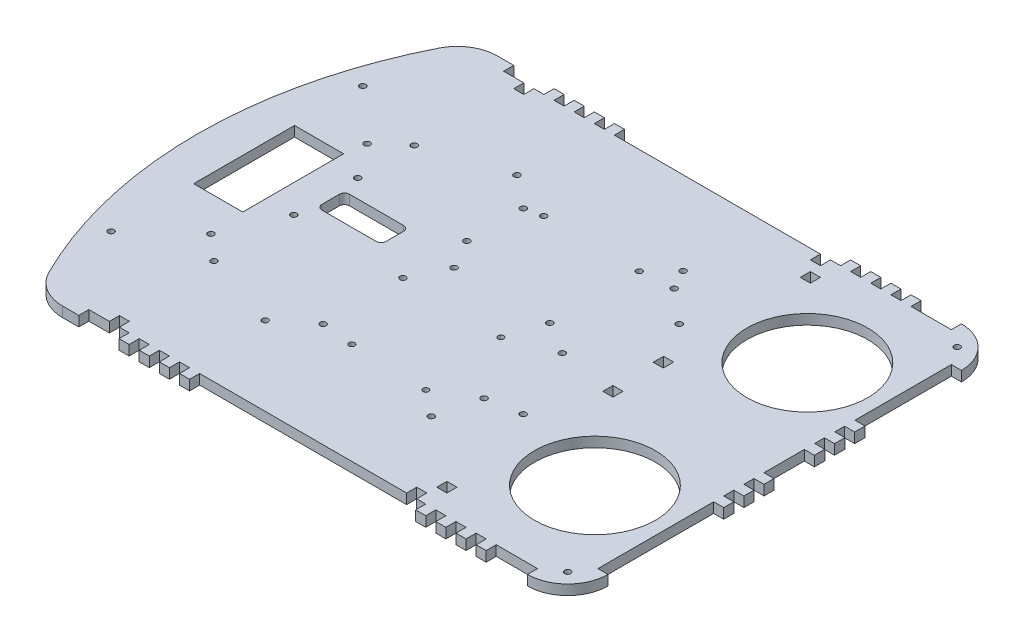
SolidWorks part; units mm, degrees
ref_plane "Front Plane" through (0, 0, 0) normal (0, 0, 1) x (1, 0, 0)
ref_plane "Top Plane" through (0, 0, 0) normal (0, 1, 0) x (1, 0, 0)
ref_plane "Right Plane" through (0, 0, 0) normal (1, 0, 0) x (0, 0, -1)
sketch "main_base_sketch" plane through (0, 0, 0) normal (0, 1, 0) x (1, 0, 0)
  line L1 (111.125, 92.7285) -> (111.125, 23.3533) construction
  line L2 (111.125, -38.1761) -> (111.125, 0) construction
  line L3 (111.125, -99.4864) -> (111.125, -136.4602) construction
  line L4 (111.125, -38.1761) -> (111.125, -99.4864) construction
  line L5 (111.125, 23.3533) -> (111.125, 0) construction
  line L7 (111.125, 92.7285) -> (111.125, 23.3533) construction
  line L9 (111.125, 0) -> (111.125, 23.3533) construction
  line L10 (111.125, 0) -> (111.125, -38.1761) construction
  line L11 (111.125, 0) -> (111.125, -38.1761) construction
  line L20 (-111.125, 0) -> (111.125, 0) construction
  line L22 (111.125, 130.8285) -> (117.475, 130.8285) construction
  line L24 (-94.9614, 130.8285) -> (-94.9614, 124.4785) construction
  line L25 (-94.9614, 124.4785) -> (-82.2614, 124.4785)
  line L26 (187.325, 130.8285) -> (187.325, 124.4785)
  line L27 (-95.6016, -142.8102) -> (111.125, -142.8102) construction
  line L28 (-95.6016, -142.8102) -> (-95.6016, -136.4602)
  line L29 (-95.6016, -136.4602) -> (-82.6643, -136.4602)
  line L30 (187.325, -142.8102) -> (187.325, -136.4602)
  line L32 (-94.9614, 130.8285) -> (-25.1114, 130.8285) construction
  line L33 (111.125, -142.8102) -> (187.325, -142.8102) construction
  line L34 (111.125, -136.4602) -> (111.125, -142.8102) construction
  line L36 (111.125, -136.4602) -> (111.125, -142.8102) construction
  line L37 (-56.8614, 130.8285) -> (-50.5114, 130.8285)
  line L38 (111.125, 12.7) -> (117.4276, 12.7)
  line L39 (-42.259, -8.6817) -> (-76.4089, -8.6817)
  line L40 (-39.084, -5.5067) -> (-39.084, 5.5067)
  line L41 (-42.259, 8.6817) -> (-76.4089, 8.6817)
  line L42 (-79.5839, -5.5067) -> (-79.5839, 5.5067)
  line L43 (-39.084, -8.6817) -> (-79.5839, 8.6817) construction
  line L44 (-39.084, 8.6817) -> (-79.5839, -8.6817) construction
  line L46 (61.595, 63.5) -> (93.345, 63.5) construction
  line L47 (61.595, 63.5) -> (61.595, -63.5) construction
  line L48 (61.595, -63.5) -> (93.345, -63.5) construction
  line L49 (93.345, 63.5) -> (93.345, -63.5) construction
  line L50 (61.595, 63.5) -> (93.345, -63.5) construction
  line L51 (61.595, -63.5) -> (93.345, 63.5) construction
  line L52 (111.125, 12.7) -> (111.125, 19.2555)
  line L53 (111.125, 23.3533) -> (111.125, 0) construction
  line L54 (111.125, 19.2555) -> (117.4276, 19.2555)
  line L55 (-94.9614, 130.8285) -> (-25.1114, 130.8285) construction
  line L58 (111.125, 124.4785) -> (111.125, 92.7285) construction
  line L61 (-95.6016, -142.8102) -> (111.125, -142.8102) construction
  line L62 (111.125, -99.4864) -> (111.125, -136.4602) construction
  line L63 (111.125, 130.8285) -> (117.475, 130.8285) construction
  line L64 (111.125, 124.4785) -> (111.125, 92.7285) construction
  line L65 (111.125, -142.8102) -> (187.325, -142.8102) construction
  line L66 (212.725, 105.4285) -> (212.725, -117.4102) construction
  line L67 (117.4276, 12.7) -> (117.4276, 19.2555)
  line L68 (111.125, -12.7) -> (117.475, -12.7)
  line L69 (111.125, -12.7) -> (111.125, -19.05)
  line L70 (111.125, -19.05) -> (117.475, -19.05)
  line L71 (117.475, -12.7) -> (117.475, -19.05)
  line L72 (111.125, 105.4285) -> (117.475, 105.4285)
  line L73 (111.125, 105.4285) -> (111.125, 111.7785)
  line L74 (111.125, 111.7785) -> (117.475, 111.7785)
  line L75 (117.475, 105.4285) -> (117.475, 111.7785)
  line L76 (111.125, -117.4102) -> (117.475, -117.4102)
  line L77 (111.125, -117.4102) -> (111.125, -123.7602)
  line L78 (111.125, -123.7602) -> (117.475, -123.7602)
  line L79 (117.475, -117.4102) -> (117.475, -123.7602)
  line L80 (212.725, 105.4285) -> (206.375, 105.4285)
  line L81 (212.725, 105.4285) -> (212.725, -117.4102) construction
  line L82 (212.725, -117.4102) -> (206.375, -117.4102)
  line L84 (-69.5614, 130.8285) -> (-63.2114, 130.8285)
  line L85 (-69.5614, 130.8285) -> (-69.5614, 124.4785)
  line L86 (-69.5614, 124.4785) -> (-63.2114, 124.4785) construction
  line L87 (-63.2114, 130.8285) -> (-63.2114, 124.4785)
  line L88 (-56.8614, 130.8285) -> (-56.8614, 124.4785)
  line L89 (-56.8614, 124.4785) -> (-50.5114, 124.4785) construction
  line L90 (-50.5114, 130.8285) -> (-50.5114, 124.4785)
  line L91 (-44.1614, 130.8285) -> (-37.8114, 130.8285)
  line L92 (-44.1614, 130.8285) -> (-44.1614, 124.4785)
  line L93 (-44.1614, 124.4785) -> (-37.8114, 124.4785) construction
  line L94 (-37.8114, 130.8285) -> (-37.8114, 124.4785)
  line L95 (-31.4614, 130.8285) -> (-25.1114, 130.8285)
  line L96 (-31.4614, 130.8285) -> (-31.4614, 124.4785)
  line L97 (-31.4614, 124.4785) -> (-25.1114, 124.4785) construction
  line L98 (-25.1114, 130.8285) -> (-25.1114, 124.4785)
  line L99 (-69.5614, 124.4785) -> (-63.2114, 124.4785) construction
  line L100 (-63.2114, 124.4785) -> (-56.8614, 124.4785)
  line L101 (-56.8614, 124.4785) -> (-50.5114, 124.4785) construction
  line L102 (-50.5114, 124.4785) -> (-44.1614, 124.4785)
  line L103 (-44.1614, 124.4785) -> (-37.8114, 124.4785) construction
  line L104 (-37.8114, 124.4785) -> (-31.4614, 124.4785)
  line L105 (-31.4614, 124.4785) -> (-25.1114, 124.4785) construction
  line L106 (-25.1114, 124.4785) -> (104.775, 124.4785)
  line L107 (149.225, 130.8285) -> (142.875, 130.8285)
  line L108 (161.925, 130.8285) -> (155.575, 130.8285)
  line L109 (161.925, 130.8285) -> (161.925, 124.4785)
  line L110 (161.925, 124.4785) -> (155.575, 124.4785) construction
  line L111 (155.575, 130.8285) -> (155.575, 124.4785)
  line L112 (149.225, 130.8285) -> (149.225, 124.4785)
  line L114 (142.875, 130.8285) -> (142.875, 124.4785)
  line L115 (136.525, 130.8285) -> (130.175, 130.8285)
  line L116 (136.525, 130.8285) -> (136.525, 124.4785)
  line L118 (130.175, 130.8285) -> (130.175, 124.4785)
  line L119 (123.825, 130.8285) -> (117.475, 130.8285) construction
  line L120 (123.825, 130.8285) -> (123.825, 124.4785)
  line L122 (117.475, 130.8285) -> (117.475, 124.4785) construction
  line L123 (117.475, 130.8285) -> (123.825, 130.8285) construction
  line L124 (206.375, 105.4285) -> (206.375, 44.6555)
  line L127 (117.475, 130.8285) -> (117.475, 124.4785) construction
  line L128 (117.475, 130.8285) -> (117.475, 124.4785) construction
  line L129 (145.8534, 124.4785) -> (130.175, 124.4785) [skipped]
  line L130 (149.225, 124.4785) -> (146.7264, 124.4785) [skipped]
  line L131 (123.825, 124.4785) -> (130.175, 124.4785)
  line L132 (136.525, 124.4785) -> (142.875, 124.4785)
  line L133 (149.225, 124.4785) -> (155.575, 124.4785)
  line L134 (161.925, 124.4785) -> (187.325, 124.4785)
  line L135 (133.0367, 124.4785) -> (117.475, 124.4785) [skipped]
  line L136 (123.825, 130.8285) -> (187.325, 130.8285) construction
  line L137 (117.475, 130.8285) -> (123.825, 130.8285) construction
  line L138 (123.825, 130.8285) -> (187.325, 130.8285) construction
  line L139 (-25.1114, 130.8285) -> (111.125, 130.8285) construction
  line L140 (-25.1114, 130.8285) -> (111.125, 130.8285) construction
  line L141 (111.125, 130.8285) -> (111.125, 124.4785) construction
  line L142 (111.125, 130.8285) -> (111.125, 124.4785) construction
  line L143 (123.825, 130.8285) -> (117.475, 130.8285)
  line L144 (117.475, 130.8285) -> (117.475, 124.4785)
  line L151 (206.375, -12.7) -> (212.725, -12.7)
  line L152 (206.375, -12.7) -> (206.375, -19.05) construction
  line L153 (206.375, -19.05) -> (212.725, -19.05)
  line L154 (212.725, -12.7) -> (212.725, -19.05)
  line L155 (206.375, -12.7) -> (206.375, -19.05) construction
  line L156 (206.375, -19.05) -> (206.375, -25.4)
  line L157 (206.375, 19.2555) -> (212.725, 19.2555)
  line L158 (212.725, 19.2555) -> (212.725, 12.7)
  line L159 (212.725, 12.7) -> (206.375, 12.7)
  line L160 (206.375, 24.1792) -> (206.375, 19.2555)
  line L161 (206.375, 12.7) -> (206.375, -12.7)
  line L162 (-70.2016, -136.4602) -> (-70.2016, -142.8102)
  line L163 (-70.2016, -142.8102) -> (-63.8516, -142.8102)
  line L164 (-63.8516, -142.8102) -> (-63.8516, -136.4602)
  line L165 (-70.2016, -136.4602) -> (-63.8516, -136.4602) construction
  line L166 (-63.8516, -136.4602) -> (-57.5016, -136.4602)
  line L167 (-57.5016, -142.8102) -> (-51.1516, -142.8102)
  line L168 (-57.5016, -136.4602) -> (-57.5016, -142.8102)
  line L169 (-51.1516, -142.8102) -> (-51.1516, -136.4602)
  line L170 (-44.8016, -142.8102) -> (-38.4516, -142.8102)
  line L171 (-44.8016, -136.4602) -> (-44.8016, -142.8102)
  line L172 (-38.4516, -142.8102) -> (-38.4516, -136.4602)
  line L173 (-32.1016, -142.8102) -> (-25.7516, -142.8102)
  line L174 (-32.1016, -136.4602) -> (-32.1016, -142.8102)
  line L175 (-25.7516, -142.8102) -> (-25.7516, -136.4602)
  line L176 (-57.5016, -136.4602) -> (-51.1516, -136.4602) construction
  line L177 (-51.1516, -136.4602) -> (-44.8016, -136.4602)
  line L178 (-44.8016, -136.4602) -> (-38.4516, -136.4602) construction
  line L179 (-38.4516, -136.4602) -> (-32.1016, -136.4602)
  line L180 (-32.1016, -136.4602) -> (-25.7516, -136.4602) construction
  line L181 (-25.7516, -136.4602) -> (104.775, -136.4602)
  line L182 (161.2847, -136.4602) -> (161.2847, -142.8102)
  line L183 (161.2847, -142.8102) -> (154.9347, -142.8102)
  line L184 (154.9347, -142.8102) -> (154.9347, -136.4602)
  line L185 (148.5847, -136.4602) -> (148.5847, -142.8102)
  line L186 (148.5847, -142.8102) -> (142.2347, -142.8102)
  line L187 (142.2347, -142.8102) -> (142.2347, -136.4602)
  line L188 (135.8847, -136.4602) -> (135.8847, -142.8102)
  line L189 (135.8847, -142.8102) -> (129.5347, -142.8102)
  line L190 (129.5347, -142.8102) -> (129.5347, -136.4602)
  line L191 (123.1847, -136.4602) -> (123.1847, -142.8102)
  line L192 (123.1847, -142.8102) -> (116.8347, -142.8102)
  line L193 (116.8347, -142.8102) -> (116.8347, -136.4602)
  line L194 (154.9347, -136.4602) -> (161.2847, -136.4602) construction
  line L195 (161.2847, -136.4602) -> (187.325, -136.4602)
  line L196 (142.2347, -136.4602) -> (148.5847, -136.4602) construction
  line L197 (148.5847, -136.4602) -> (154.9347, -136.4602)
  line L198 (129.5347, -136.4602) -> (135.8847, -136.4602) construction
  line L199 (135.8847, -136.4602) -> (142.2347, -136.4602)
  line L200 (116.8347, -136.4602) -> (123.1847, -136.4602) construction
  line L201 (123.1847, -136.4602) -> (129.5347, -136.4602)
  line L202 (212.725, 25.4) -> (206.375, 25.4)
  line L203 (212.725, 31.9555) -> (212.725, 25.4)
  line L204 (206.375, 31.9555) -> (212.725, 31.9555)
  line L205 (212.725, 38.1) -> (206.375, 38.1)
  line L206 (212.725, 44.6555) -> (212.725, 38.1)
  line L207 (206.375, 44.6555) -> (212.725, 44.6555)
  line L208 (206.375, 31.9555) -> (206.375, 25.4) construction
  line L209 (206.375, 25.4) -> (206.375, 24.1792)
  line L210 (206.375, 44.6555) -> (206.375, 38.1) construction
  line L211 (206.375, 38.1) -> (206.375, 31.9555)
  line L212 (206.375, -31.75) -> (212.725, -31.75)
  line L213 (212.725, -25.4) -> (212.725, -31.75)
  line L214 (206.375, -25.4) -> (212.725, -25.4)
  line L215 (206.375, -44.45) -> (212.725, -44.45)
  line L216 (212.725, -38.1) -> (212.725, -44.45)
  line L217 (206.375, -38.1) -> (212.725, -38.1)
  line L218 (206.375, -25.4) -> (206.375, -31.75) construction
  line L219 (206.375, -31.75) -> (206.375, -38.1)
  line L220 (206.375, -38.1) -> (206.375, -44.45) construction
  line L221 (206.375, -44.45) -> (206.375, -117.4102)
  line L225 (-95.5505, 130.8285) -> (-157.7358, 130.8285) construction
  line L229 (-131.2964, 28.9076) -> (-100.3373, 28.9076)
  line L230 (-131.2964, 28.9076) -> (-131.2964, -34.6891)
  line L231 (-131.2964, -34.6891) -> (-100.3373, -34.6891)
  line L238 (-100.3373, 28.9076) -> (-100.3373, -34.6891)
  line L248 (-94.9614, 130.8285) -> (-95.5505, 130.8285) construction
  line L254 (-94.9614, 130.8285) -> (-95.5505, 130.8285) construction
  line L257 (-94.9614, 130.8285) -> (-105.2412, 130.8285)
  line L258 (-95.5505, 130.8285) -> (-94.9614, 130.8285) construction
  line L259 (-95.6016, -142.8102) -> (-105.7982, -142.8102)
  line L260 (-94.9614, 124.4785) -> (-94.9614, 130.8285)
  line L261 (-94.9614, 130.8285) -> (-95.5505, 130.8285) construction
  line L262 (-82.2614, 124.4785) -> (-75.9114, 124.4785) construction
  line L263 (-82.2614, 124.4785) -> (-75.9114, 124.4785) construction
  line L264 (-82.2614, 124.4785) -> (-82.2614, 118.1285)
  line L265 (-82.2614, 118.1285) -> (-75.9114, 118.1285)
  line L266 (-75.9114, 124.4785) -> (-75.9114, 118.1285)
  line L267 (-97.1554, -142.8102) -> (-95.6016, -142.8102) construction
  line L269 (-75.9114, 124.4785) -> (-69.5614, 124.4785)
  line L270 (104.775, 124.4785) -> (111.125, 124.4785) construction
  line L271 (111.125, 124.4785) -> (104.775, 124.4785) construction
  line L272 (111.125, 124.4785) -> (111.125, 118.1285)
  line L274 (111.125, 118.1285) -> (104.775, 118.1285)
  line L280 (104.775, 124.4785) -> (104.775, 118.1285)
  line L281 (111.125, 124.4785) -> (117.475, 124.4785)
  line L282 (104.775, -136.4602) -> (111.125, -136.4602) construction
  line L285 (111.125, -136.4602) -> (104.775, -136.4602) construction
  line L286 (111.125, -136.4602) -> (111.125, -130.1018)
  line L289 (111.125, -130.1018) -> (104.775, -130.1018)
  line L291 (104.775, -136.4602) -> (104.775, -130.1018)
  line L292 (111.125, -136.4602) -> (116.8347, -136.4602)
  line L293 (-82.6643, -136.4602) -> (-76.4089, -136.4602) construction
  line L294 (-94.9614, 130.8285) -> (-95.5505, 130.8285) construction
  line L295 (-157.7358, 130.8285) -> (-157.7358, -142.8102) construction
  line L296 (-157.7358, -142.8102) -> (-97.1554, -142.8102) construction
  line L297 (-95.5505, 130.8285) -> (-157.7358, 130.8285) construction
  line L298 (-82.6643, -136.4602) -> (-76.4089, -136.4602) construction
  line L299 (-82.6643, -136.4602) -> (-82.6643, -130.1018)
  line L300 (-82.6643, -130.1018) -> (-76.4089, -130.1018)
  line L301 (-76.4089, -136.4602) -> (-76.4089, -130.1018)
  line L302 (-76.4089, -136.4602) -> (-70.2016, -136.4602)
  circle A0 centre (-82.6643, 55.7457) radius 1.905
  circle A1 centre (-13.8303, 55.7457) radius 1.905
  arc A2 (-76.4089, -8.6817) -> (-79.5839, -5.5067) centre (-76.4089, -5.5067) cw
  arc A3 (-42.259, -8.6817) -> (-39.084, -5.5067) centre (-42.259, -5.5067) ccw
  arc A4 (-39.084, 5.5067) -> (-42.259, 8.6817) centre (-42.259, 5.5067) ccw
  arc A5 (-76.4089, 8.6817) -> (-79.5839, 5.5067) centre (-76.4089, 5.5067) ccw
  circle A10 centre (-3.2843, 57.9936) radius 1.905
  circle A11 centre (-13.8303, 20.1549) radius 1.905
  circle A12 centre (-3.2843, 1.5294) radius 1.905
  circle A13 centre (-82.6643, 20.1549) radius 1.905
  circle A14 centre (-82.6643, -20.1549) radius 1.905
  circle A15 centre (-13.8303, -20.1549) radius 1.905
  circle A16 centre (-82.6643, -70.5685) radius 1.905
  circle A17 centre (-13.8303, -70.5685) radius 1.905
  circle A18 centre (6.29, -72.5476) radius 1.796
  circle A19 centre (54.55, -74.1351) radius 1.796
  circle A20 centre (49.47, -21.7476) radius 1.796
  circle A21 centre (57.0407, 1.5294) radius 1.905
  circle A22 centre (57.0407, 57.9936) radius 1.905
  circle A23 centre (-98.425, 41.8224) radius 1.905
  circle A24 centre (-34.0871, 71.9636) radius 1.905
  circle A25 centre (70.6863, 71.9636) radius 1.905
  circle A26 centre (98.425, 41.8224) radius 1.905
  circle A27 centre (98.425, -56.6452) radius 1.905
  circle A28 centre (70.6863, -86.7864) radius 1.905
  circle A29 centre (-34.0871, -86.7864) radius 1.905
  circle A30 centre (-98.425, -56.6452) radius 1.905
  circle A31 centre (77.47, -60.325) radius 1.905
  circle A32 centre (77.47, 59.5313) radius 1.905
  circle A33 centre (77.47, -10.9537) radius 1.905
  arc A34 (212.725, -117.4102) -> (187.325, -142.8102) centre (187.325, -117.4102) cw
  arc A35 (212.725, 105.4285) -> (187.325, 130.8285) centre (187.325, 105.4285) ccw
  circle A37 centre (160.02, 60.9785) radius 38.1
  circle A38 centre (160.02, -72.9602) radius 38.1
  arc A41 (-127.9188, 116.8691) -> (-128.5327, -128.7374) centre (116.7138, -6.5464) ccw
  arc A42 (-127.9188, 116.8691) -> (-105.2412, 130.8285) centre (-105.2412, 105.4285) cw
  arc A43 (-128.5327, -128.7374) -> (-105.7982, -142.8102) centre (-105.7982, -117.4102) ccw
  circle A44 centre (-131.2964, 71.9636) radius 1.905
  circle A45 centre (-131.2964, -86.7864) radius 1.905
  circle A46 centre (198.6177, 116.8691) radius 1.905
  circle A47 centre (198.6177, -128.7374) radius 1.905
  point P16 (-120.3614, 130.8285)
  point P19 (212.725, -142.8102)
  point P40 (-59.334, 0)
  point P46 (-121.0016, -142.8102)
  point P111 (77.47, -63.5)
  point P113 (77.47, 0)
  point P123 (0, 0)
  dimension "D1" = 3.175
  dimension "D44" = 3.81
  dimension "D45" = 3.81
  dimension "D46" = 3.81
  dimension "D47" = 3.592
  dimension "D48" = 3.592
  dimension "D49" = 3.592
  dimension "D7" = 63.5
  dimension "D12" = 25.4
  dimension "D13" = 25.4
  dimension "D21" = 63.5
  dimension "D24" = 76.2
  dimension "D26" = 76.2
  dimension "D14" = 25.4
  dimension "D30" = 3.81
  dimension "D31" = 6.35
  dimension "D8" = 4
  dimension "D9" = 40.4999
  dimension "D10" = 17.3633
  dimension "D11" = 4
  dimension "D15" = 104.7734
  dimension "D16" = 74.077
  dimension "D17" = 104.835
  dimension "D18" = 12.7
  dimension "D19" = 6.35
  dimension "D20" = 6.35
  dimension "D22" = 40.4387
  dimension "D23" = 54.0843
  dimension "D25" = 60.325
  dimension "D27" = 10.2799
  dimension "D28" = 10.1966
  dimension "D29" = 6.5555
  dimension "D32" = 6.35
  dimension "D33" = 6.35
  dimension "D34" = 68.834
  dimension "D35" = 48.26
  dimension "D36" = 6.35
  dimension "D37" = 20.1549
  dimension "D38" = 20.1549
  dimension "D39" = 56.4642
  dimension "D40" = 35.7997
  dimension "D41" = 54.0843
  dimension "D42" = 61.655
  dimension "D43" = 23.277
  dimension "D50" = 1.5875
  dimension "D51" = 127
  dimension "D52" = 31.75
  dimension "D53" = 17.78
  dimension "D54" = 3.175
  dimension "D55" = 3.9688
  dimension "D56" = 70.485
  dimension "D57" = 38.1
  dimension "D58" = 6.35
  dimension "D59" = 101.6
  dimension "D60" = 6.3026
  dimension "D61" = 12.7
  dimension "D62" = 12.7
  dimension "D63" = 6.35
  dimension "D64" = 6.35
  dimension "D65" = 6.35
  dimension "D66" = 6.35
  dimension "D67" = 12.7
  dimension "D68" = 12.7
  dimension "D69" = 6.35
  dimension "D70" = 6.35
  dimension "D71" = 4
  dimension "D72" = 6.35
  dimension "D73" = 6.35
  dimension "D74" = 6.35
  dimension "D76" = 3
  dimension "D77" = 3
  dimension "D78" = 6.3585
  dimension "D75" = 4
extrude "main_base" add sketch "main_base_sketch" along normal blind 6.35
